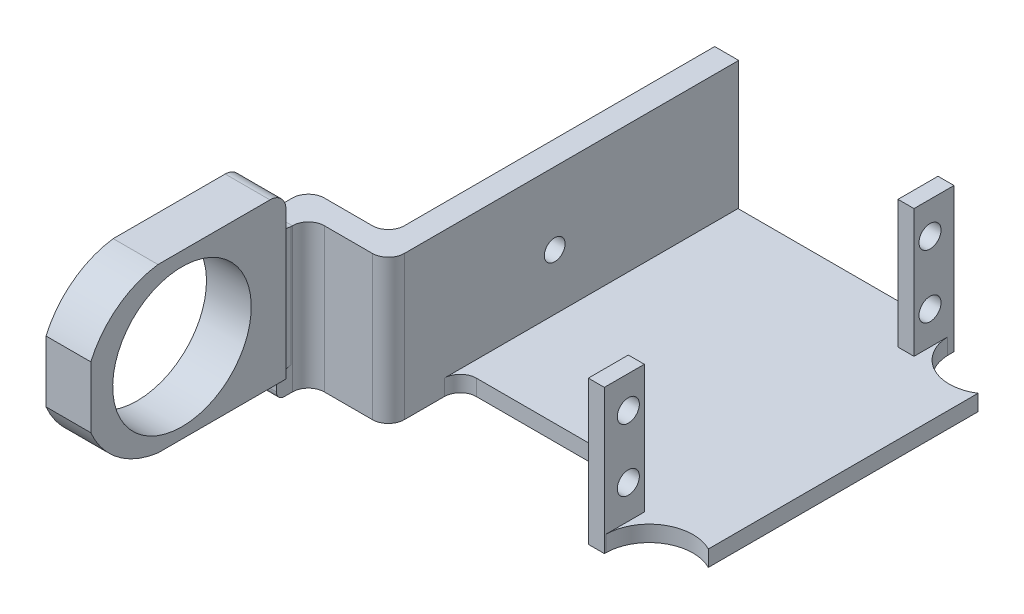
SolidWorks part; units mm, degrees
ref_plane "Front Plane" through (0, 0, 0) normal (0, 0, 1) x (1, 0, 0)
ref_plane "Top Plane" through (0, 0, 0) normal (0, 1, 0) x (1, 0, 0)
ref_plane "Right Plane" through (0, 0, 0) normal (1, 0, 0) x (0, 0, -1)
sketch "Sketch1" plane through (0, 0, 0) normal (0, 1, 0) x (1, 0, 0)
  line L0 (-13.6183, 25.0712) -> (18.1317, 25.0712)
  line L1 (-13.6183, 25.0712) -> (-13.6183, -30.4448)
  line L2 (-13.6183, -30.4448) -> (18.1317, -30.4448)
  line L3 (18.1317, 25.0712) -> (18.1317, -30.4448)
  dimension "D1" = 31.75
  dimension "D2" = 55.516
extrude "Boss-Extrude1" add sketch "Sketch1" along normal blind 2.54 contours L0 L3 L2 L1
sketch "Sketch10" plane through (0, 0, 0) normal (0, -1, 0) x (-1, 0, 0)
  line L1 (13.6183, -30.4448) -> (17.4283, -30.4448)
  line L2 (13.6183, -30.4448) -> (13.6183, 25.1771)
  line L3 (13.6183, 25.1771) -> (17.4283, 25.1771)
  line L4 (17.4283, -30.4448) -> (17.4283, 25.1771)
  line L5 (17.4283, -30.4448) -> (26.3183, -30.4448)
  line L6 (17.4283, -30.4448) -> (17.4283, -26.6348)
  line L7 (17.4283, -26.6348) -> (26.3183, -26.6348)
  line L8 (26.3183, -30.4448) -> (26.3183, -26.6348)
  line L9 (26.3183, -26.6348) -> (30.1283, -26.6348)
  line L10 (26.3183, -26.6348) -> (26.3183, -35.5263)
  line L11 (26.3183, -35.5263) -> (30.1283, -35.5263)
  line L12 (30.1283, -26.6348) -> (30.1283, -35.5263)
  line M5 (13.6183, -30.4448) -> (13.6183, 25.0712)
  dimension "D1" = 3.81
  dimension "D2" = 3.81
  dimension "D3" = 3.81
  dimension "D4" = 8.89
extrude "Boss-Extrude6" add sketch "Sketch10" against normal blind 22.86 contours L1 L4 L3 L2 M5 | L5 L8 L7 L4 | L12 L9 L8 L10 L11 region at (-15.5233, 0, 2.6339) region at (-21.8733, 0, 28.5398) region at (-28.2233, 0, 31.0805)
sketch "Sketch12" plane through (0, 0, 35.5263) normal (0, 0, 1) x (1, 0, 0)
  line L0 (-26.3183, 22.86) -> (-30.1283, 22.86) construction
  line L1 (-31.9063, 29.718) -> (-24.7943, 29.718)
  line L2 (-31.9063, 29.718) -> (-31.9063, 3.81)
  line L3 (-31.9063, 3.81) -> (-24.7943, 3.81)
  line L4 (-24.7943, 29.718) -> (-24.7943, 3.81)
  line L5 (-26.3183, 0) -> (-30.1283, 0) construction
  line L6 (-26.3183, 22.86) -> (-26.3183, 0) construction
  dimension "D1" = 6.858
  dimension "D2" = 7.112
  dimension "D3" = 3.81
  dimension "D4" = 1.524
extrude "Boss-Extrude7" add sketch "Sketch12" along normal blind 31.75
sketch "Sketch13" plane through (-31.9063, 0, 0) normal (-1, 0, 0) x (0, 0, 1)
  line L1 (67.2763, 19.3962) -> (67.2763, 29.718)
  line L2 (67.2763, 29.718) -> (67.2763, 3.81) construction
  line L3 (-25.1771, 22.86) -> (-25.1771, 0) construction
  line L4 (26.6348, 22.86) -> (-25.1771, 22.86) construction
  line L6 (55.8463, 29.718) -> (67.2763, 29.718)
  line L7 (67.2763, 14.3162) -> (67.2763, 3.81)
  line L9 (55.8463, 3.81) -> (67.2763, 3.81)
  line L10 (67.2763, 14.3162) -> (67.2763, 3.81)
  line L11 (67.2763, 14.3162) -> (67.2763, 16.8562)
  line L12 (67.2763, 3.81) -> (67.2763, 14.3162)
  line L13 (67.2763, 3.81) -> (67.2763, 29.718)
  line L14 (67.2763, 19.3962) -> (67.2763, 16.8562)
  line L15 (67.2763, 14.3162) -> (67.2763, 3.81)
  circle A0 centre (52.0363, 16.51) radius 11
  circle A1 centre (4.0329, 11.43) radius 1.65
  arc A4 (55.8463, 29.718) -> (67.2763, 19.3962) centre (54.0294, 16.2166) cw
  arc A5 (67.2763, 14.3162) -> (55.8463, 3.81) centre (54.0767, 17.2059) cw
  point P2 (0, 0)
  point P3 (0, 0)
  line M10 (35.5263, 3.81) -> (67.2763, 3.81)
  line M11 (67.2763, 3.81) -> (67.2763, 29.718)
  line M12 (67.2763, 29.718) -> (35.5263, 29.718)
  dimension "D4" = 3.3
  dimension "D3" = 15.24
  dimension "D5" = 29.21
  dimension "D6" = 11.43
  dimension "D11" = 0
extrude "Cut-Extrude5" cut sketch "Sketch13" against normal blind 21.59 contours A5 M11 M10 | A4 M12 M11 | A0 | A1 region at (-31.9063, 27.0153, 64.3904) region at (-31.9063, 6.5371, 64.4024) region at (-31.9063, 16.51, 52.0363)
sketch "Sketch14" plane through (-31.9063, 0, 0) normal (-1, 0, 0) x (0, 0, 1)
  line L1 (67.2763, 23.419) -> (66.5143, 23.419)
  line L2 (67.2763, 23.419) -> (67.2763, 9.3639)
  line L3 (67.2763, 9.3639) -> (66.5143, 9.3639)
  line L4 (66.5143, 23.419) -> (66.5143, 9.3639)
  point P9 (66.6432, 21.5044)
  dimension "D1" = 0.762
extrude "Cut-Extrude6" cut sketch "Sketch14" against normal blind 12.7
sketch "Sketch15" plane through (0, 0, 0) normal (0, -1, 0) x (1, 0, 0)
  line L1 (18.1317, -25.0712) -> (20.6717, -25.0712)
  line L2 (18.1317, -25.0712) -> (18.1317, -18.7212)
  line L3 (18.1317, -18.7212) -> (20.6717, -18.7212)
  line L4 (20.6717, -25.0712) -> (20.6717, -18.7212)
  line L5 (18.1317, 30.4448) -> (20.6717, 30.4448)
  line L6 (18.1317, 30.4448) -> (18.1317, 24.0948)
  line L7 (18.1317, 24.0948) -> (20.6717, 24.0948)
  line L8 (20.6717, 30.4448) -> (20.6717, 24.0948)
  dimension "D2" = 6.35
  dimension "D3" = 6.35
  dimension "D4" = 2.54
  dimension "D5" = 2.54
extrude "Boss-Extrude8" add sketch "Sketch15" against normal blind 22.86
sketch "Sketch16" plane through (20.6717, 0, 0) normal (1, 0, 0) x (0, 0, -1)
  line L0 (-24.0948, 22.86) -> (-30.4448, 22.86) construction
  line L1 (-30.4448, 22.86) -> (-30.4448, 0) construction
  line L3 (25.0712, 22.86) -> (18.7212, 22.86) construction
  line L4 (25.0712, 22.86) -> (25.0712, 0) construction
  circle A0 centre (-26.6348, 7.874) radius 1.75
  circle A1 centre (-26.6348, 17.78) radius 1.75
  circle A2 centre (21.2612, 7.78) radius 1.75
  circle A3 centre (21.2612, 17.78) radius 1.75
  point P14 (0, 0)
  point P17 (0, 0)
  dimension "D1" = 3.5
  dimension "D2" = 3.5
  dimension "D3" = 3.5
  dimension "D4" = 3.5
  dimension "D5" = 5.08
  dimension "D6" = 3.81
  dimension "D7" = 3.81
  dimension "D8" = 9.906
  dimension "D9" = 3.81
  dimension "D10" = 5.08
  dimension "D11" = 10
  dimension "D12" = 3.81
extrude "Cut-Extrude7" cut sketch "Sketch16" against normal blind 7.62
sketch "Sketch17" plane through (18.1317, 0, 0) normal (1, 0, 0) x (0, 0, -1)
  line L1 (-24.0948, 0) -> (18.7212, 0)
  line L2 (-24.0948, 0) -> (-24.0948, 2.54)
  line L3 (-24.0948, 2.54) -> (18.7212, 2.54)
  line L4 (18.7212, 0) -> (18.7212, 2.54)
extrude "Boss-Extrude9" add sketch "Sketch17" along normal blind 12.7
sketch "Sketch18" plane through (0, 2.54, 0) normal (0, 1, 0) x (1, 0, 0)
  line L7 (20.6717, 18.7212) -> (25.7517, 18.7212)
  line L8 (20.6717, 18.7212) -> (20.6717, 25.0712)
  line L9 (20.6717, 25.0712) -> (25.7517, 25.0712)
  line L10 (25.7517, 18.7212) -> (25.7517, 25.0712)
  line L11 (20.6717, -24.0948) -> (25.7517, -24.0948)
  line L12 (20.6717, -24.0948) -> (20.6717, -30.4448)
  line L13 (20.6717, -30.4448) -> (25.7517, -30.4448)
  line L14 (25.7517, -24.0948) -> (25.7517, -30.4448)
  dimension "D3" = 5.08
  dimension "D1" = 6.35
  dimension "D2" = 6.35
  dimension "D4" = 5.08
extrude "Boss-Extrude10" add sketch "Sketch18" against normal blind 2.54
sketch "Sketch19" plane through (0, 2.54, 0) normal (0, 1, 0) x (1, 0, 0)
  line L0 (20.6717, 25.0712) -> (20.6717, 18.7212)
  line L1 (20.6717, 18.7212) -> (30.8317, 18.7212)
  line L2 (30.8317, 18.7212) -> (30.8317, 25.0712)
  line L3 (30.8317, 25.0712) -> (20.6717, 25.0712)
  line L4 (30.8317, 18.7212) -> (30.8317, -24.0948) construction
  line L5 (30.8317, -24.0948) -> (25.7517, -24.0948) construction
  line L6 (8.6754, -19.0148) -> (-13.6183, -19.0148)
  line L7 (-13.6183, 25.0712) -> (-13.6183, -30.4448) construction
  line L8 (-13.6183, -19.0148) -> (-13.6183, -30.4448)
  line L9 (-13.6183, -30.4448) -> (18.1317, -30.4448) construction
  line L10 (-13.6183, -30.4448) -> (18.1317, -30.4448)
  arc A0 (30.8317, 18.7212) -> (20.6717, 24.6185) centre (27.2931, 24.3255) cw
  arc A1 (30.8317, -24.0948) -> (20.6717, -30.4448) centre (27.6492, -30.3058) ccw
  arc A3 (18.1317, -30.4448) -> (8.6754, -19.0148) centre (6.7714, -30.2167) ccw
  line M2 (-13.6183, 25.0712) -> (-13.6183, -30.4448)
  line M3 (-13.6183, -30.4448) -> (18.1317, -30.4448)
  line M4 (18.1317, -30.4448) -> (18.1317, -24.0948)
  line M6 (20.6717, -24.0948) -> (20.6717, -30.4448)
  line M7 (20.6717, -30.4448) -> (25.7517, -30.4448)
  line M8 (25.7517, -30.4448) -> (25.7517, -24.0948)
  line M9 (25.7517, -24.0948) -> (30.8317, -24.0948)
  line M11 (30.8317, 18.7212) -> (25.7517, 18.7212)
  line M12 (25.7517, 18.7212) -> (25.7517, 25.0712)
  line M13 (25.7517, 25.0712) -> (20.6717, 25.0712)
  line M14 (20.6717, 25.0712) -> (20.6717, 18.7212)
  dimension "D1" = 11.43
extrude "Cut-Extrude9" cut sketch "Sketch19" against normal blind 2.54 contours A0 L1 L0 M12 M13 M14 | A0 L1 M11 | A3 L6 M4 M2 M3 | A1 M9 M6 M7 M8 region at (23.5221, 2.54, -22.2419) region at (27.2931, 2.54, -18.3089) region at (1.2128, 2.54, 24.9764) region at (24.0661, 2.54, 27.2734)
fillet "Fillet1" radius 1.27 2 edges at (-28.2233, 0, 35.5263) (-28.2233, 3.81, 35.5263)
fillet "Fillet2" radius 2.54 7 edges at (-30.1283, 11.43, 26.6348) (-17.4283, 11.43, 26.6348) (-26.3183, 11.43, 30.4448) (-13.6183, 11.43, 30.4448) (-13.6183, 1.27, 19.0148) (-28.2233, 22.86, 35.5263) (-28.3503, 29.718, 35.5263)
fillet "Fillet3" radius 2.54 2 edges at (-26.3183, 14.605, 35.5263) (-30.1283, 14.605, 35.5263)
